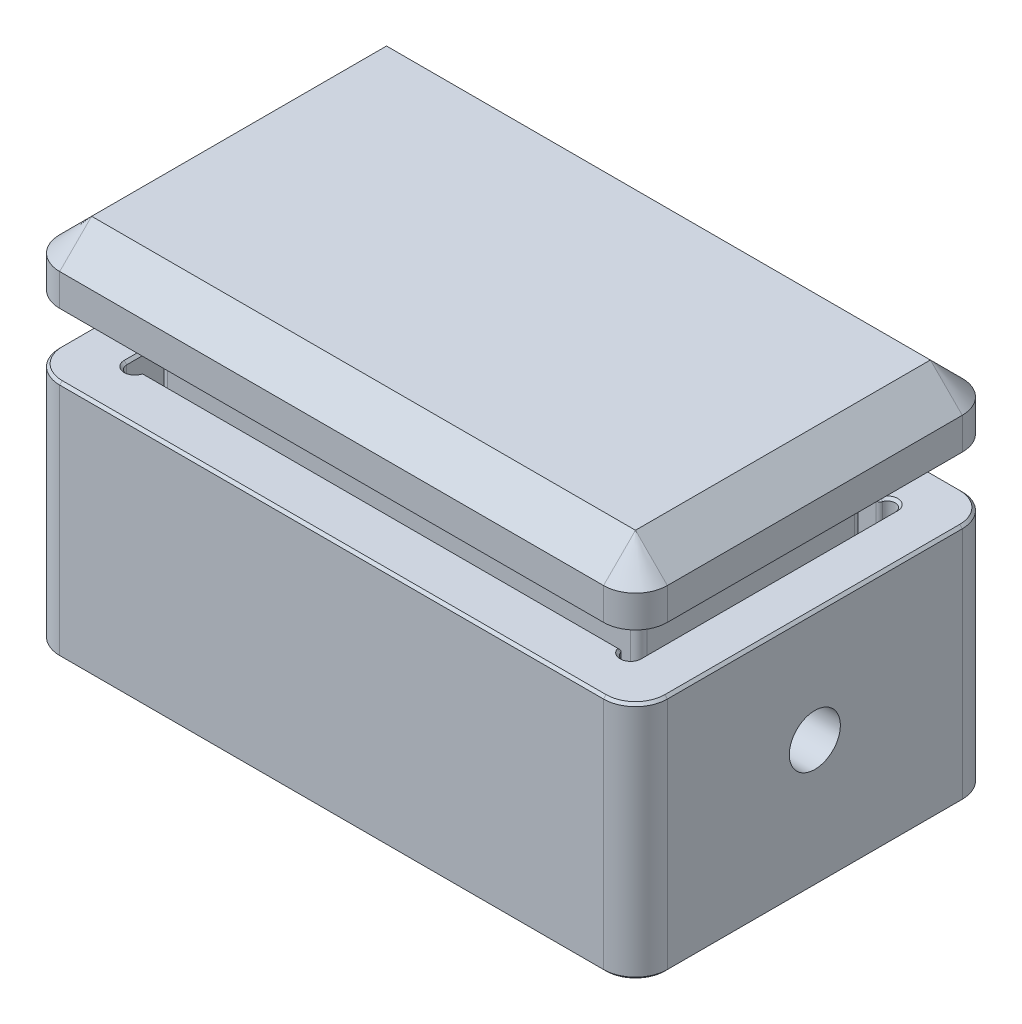
SolidWorks part; units mm, degrees
material "Nylon 101"
ref_plane "Front Plane" through (0, 0, 0) normal (0, 0, 1) x (1, 0, 0)
ref_plane "Top Plane" through (0, 0, 0) normal (0, 1, 0) x (1, 0, 0)
ref_plane "Right Plane" through (0, 0, 0) normal (1, 0, 0) x (0, 0, -1)
sketch "Sketch1" plane through (0, 0, 0) normal (0, 1, 0) x (1, 0, 0)
  line L0 (0, 12.7635) -> (50.927, 12.7635) construction
  line L1 (1.6, 0) -> (49.327, 0)
  line L2 (0, 0) -> (0, 25.527)
  line L3 (1.6, 25.527) -> (49.327, 25.527)
  line L4 (50.927, 0) -> (50.927, 25.527)
  line L5 (0, 25.527) -> (1.6, 25.527) construction
  line L6 (49.327, 25.527) -> (50.927, 25.527) construction
  line L8 (-4.7625, 30.607) -> (55.6895, 30.607)
  line L9 (-4.7625, 30.607) -> (-4.7625, -5.08)
  line L10 (-4.7625, -5.08) -> (55.6895, -5.08)
  line L11 (55.6895, 30.607) -> (55.6895, -5.08)
  arc A0 (0, 0) -> (1.6, 0) centre (0.8, 0) ccw
  arc A1 (50.927, 0) -> (49.327, 0) centre (50.127, 0) cw
  arc A2 (0, 25.527) -> (1.6, 25.527) centre (0.8, 25.527) cw
  arc A3 (50.927, 25.527) -> (49.327, 25.527) centre (50.127, 25.527) ccw
  dimension "D3" = 0.8
  dimension "D1" = 25.527
  dimension "D2" = 50.927
  dimension "D4" = 5.08
  dimension "D5" = 4.7625
  dimension "D6" = 5.08
  dimension "D7" = 4.7625
extrude "Boss-Extrude1" add sketch "Sketch1" along normal blind 23.8125
fillet "Fillet1" radius 3.175 4 edges at (-4.7625, 11.9062, -30.607) (55.6895, 11.9062, -30.607) (55.6895, 11.9062, 5.08) (-4.7625, 11.9062, 5.08)
fillet "Fillet2" radius 0.4 4 edges at (49.327, 11.9062, 0) (49.327, 11.9062, -25.527) (1.6, 11.9062, -25.527) (1.6, 11.9062, 0)
ref_plane "Plane1" through (0, 30.1625, 0) normal (0, 1, 0) x (1, 0, 0)
sketch "Sketch2" plane through (0, 30.1625, 0) normal (0, 1, 0) x (1, 0, 0)
  line L0 (50.927, 0) -> (50.927, 25.527) construction
  line L1 (0, 0) -> (50.927, 0) construction
  line L2 (0, 0) -> (0, 25.527) construction
  line L3 (0, 25.527) -> (50.927, 25.527) construction
  line L4 (52.5145, 30.607) -> (-1.5875, 30.607)
  line L5 (-4.7625, 27.432) -> (-4.7625, -1.905)
  line L6 (-1.5875, -5.08) -> (52.5145, -5.08)
  line L7 (55.6895, -1.905) -> (55.6895, 27.432)
  line L8 (52.5145, 30.607) -> (-1.5875, 30.607)
  line L9 (-4.7625, 27.432) -> (-4.7625, -1.905)
  line L10 (-1.5875, -5.08) -> (52.5145, -5.08)
  line L11 (55.6895, -1.905) -> (55.6895, 27.432)
  line L12 (50.927, 0) -> (50.927, 25.527) construction
  line L13 (48.9956, 25.527) -> (1.9314, 25.527) construction
  line L14 (1.6256, 23.9014) -> (49.3014, 23.9014)
  line L15 (49.3014, 1.6256) -> (49.3014, 23.9014)
  line L16 (1.6256, 1.6256) -> (49.3014, 1.6256)
  line L17 (1.6256, 1.6256) -> (1.6256, 23.9014)
  arc A4 (-1.5875, 30.607) -> (-4.7625, 27.432) centre (-1.5875, 27.432) ccw
  arc A5 (-4.7625, -1.905) -> (-1.5875, -5.08) centre (-1.5875, -1.905) ccw
  arc A6 (52.5145, -5.08) -> (55.6895, -1.905) centre (52.5145, -1.905) ccw
  arc A7 (55.6895, 27.432) -> (52.5145, 30.607) centre (52.5145, 27.432) ccw
  arc A8 (-1.5875, 30.607) -> (-4.7625, 27.432) centre (-1.5875, 27.432) ccw
  arc A9 (-4.7625, -1.905) -> (-1.5875, -5.08) centre (-1.5875, -1.905) ccw
  arc A10 (52.5145, -5.08) -> (55.6895, -1.905) centre (52.5145, -1.905) ccw
  arc A11 (55.6895, 27.432) -> (52.5145, 30.607) centre (52.5145, 27.432) ccw
  dimension "D1" = 0
  dimension "D2" = 1.6256
extrude "Boss-Extrude2" add sketch "Sketch2" along normal blind 6.35 separate body contours L17 L16 L15 L14 | L11 A11 L8 A8 L9 A9 L10 A10 L16 L17 L14 L15 region at (54.2632, 30.1625, -29.1807) region at (25.4635, 30.1625, -12.7635)
extrude "Boss-Extrude3" add sketch "Sketch2<4>" against normal up to surface (30.1625 mm away) contours L17 L16 L15 L14 region at (25.4635, 30.1625, -12.7635) up to face at (25.4635, 0, -12.7635)
sketch "Sketch2<4>" plane through (0, 30.1625, 0) normal (0, 1, 0) x (1, 0, 0) same geometry as "Sketch2"
chamfer "Chamfer1" distance 3.175 angle 45 8 edges at (54.7596, 36.5125, 4.1501) (25.4635, 36.5125, 5.08) (-3.8326, 36.5125, 4.1501) (-4.7625, 36.5125, -12.7635) (-3.8326, 36.5125, -29.6771) (25.4635, 36.5125, -30.607) (54.7596, 36.5125, -29.6771) (55.6895, 36.5125, -12.7635)
chamfer "Chamfer2" distance 4.7625 angle 45 4 edges at (1.6256, 0, -12.7635) (25.4635, 0, -1.6256) (49.3014, 0, -12.7635) (25.4635, 0, -23.9014)
chamfer "Chamfer3" distance 0.254 angle 45 40 edges at (50.927, 23.8125, -12.7635) (50.2623, 23.8125, -26.3155) (49.2266, 23.8125, -25.6004) (25.4635, 23.8125, -25.527) (1.7004, 23.8125, -25.6004) (0.6647, 23.8125, -26.3155) (0, 23.8125, -12.7635) (0.6647, 23.8125, 0.7885) (1.7004, 23.8125, 0.0734) (25.4635, 23.8125, 0) (49.2266, 23.8125, 0.0734) (50.2623, 23.8125, 0.7885) (54.7596, 23.8125, -29.6771) (55.6895, 23.8125, -12.7635) (54.7596, 23.8125, 4.1501) (25.4635, 23.8125, 5.08) (-3.8326, 23.8125, 4.1501) (-4.7625, 23.8125, -12.7635) (-3.8326, 23.8125, -29.6771) (25.4635, 23.8125, -30.607) (1.7004, 0, 0.0734) (0.6647, 0, 0.7885) (0, 0, -12.7635) (0.6647, 0, -26.3155) (1.7004, 0, -25.6004) (25.4635, 0, -25.527) (49.2266, 0, -25.6004) (50.2623, 0, -26.3155) (50.927, 0, -12.7635) (50.2623, 0, 0.7885) (49.2266, 0, 0.0734) (25.4635, 0, 0) (-3.8326, 0, 4.1501) (25.4635, 0, 5.08) (54.7596, 0, 4.1501) (55.6895, 0, -12.7635) (54.7596, 0, -29.6771) (25.4635, 0, -30.607) (-3.8326, 0, -29.6771) (-4.7625, 0, -12.7635)
fillet "Fillet3" radius 0.8106 4 edges at (1.6256, 17.4625, -23.9014) (49.3014, 17.4625, -1.6256) (1.6256, 17.4625, -1.6256) (49.3014, 17.4625, -23.9014)
sketch "Sketch3" plane through (55.6895, 0, 0) normal (1, 0, 0) x (0, 0, -1)
  line L2 (27.432, 23.5585) -> (-1.905, 23.5585) construction
  line L3 (12.7635, 0.254) -> (12.7635, 23.5585) construction
  line L4 (-1.905, 0.254) -> (27.432, 0.254) construction
  line L5 (-1.905, 30.1625) -> (27.432, 30.1625) construction
  circle A0 centre (12.7635, 12.7) radius 2.54
  dimension "D3" = 5.08
  dimension "D1" = 17.4625
extrude "Cut-Extrude1" cut sketch "Sketch3" against normal through all
equation "\"D3@Sketch1\"=0.4mm *2"
